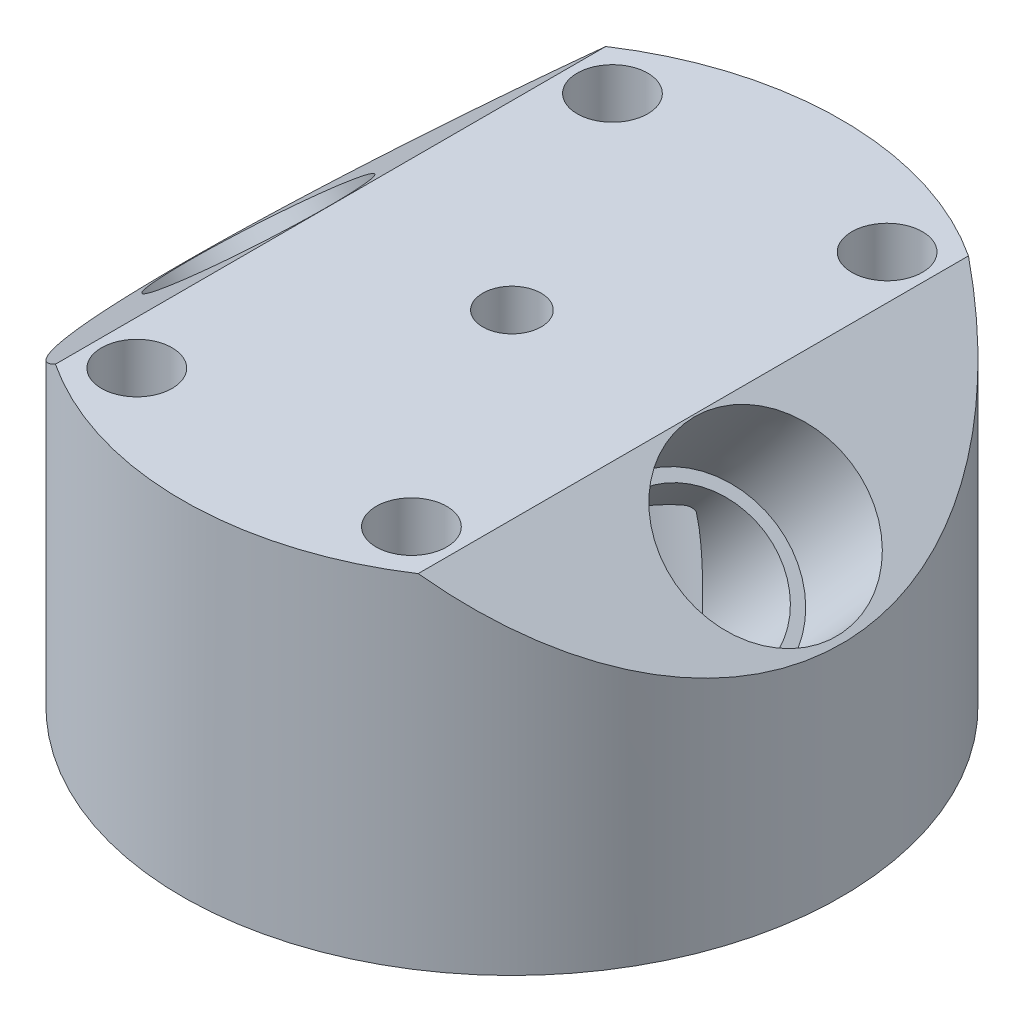
SolidWorks part; units mm, degrees
material "AISI 304"
ref_plane "Front Plane" through (0, 0, 0) normal (0, 0, 1) x (1, 0, 0)
ref_plane "Top Plane" through (0, 0, 0) normal (0, 1, 0) x (1, 0, 0)
ref_plane "Right Plane" through (0, 0, 0) normal (1, 0, 0) x (0, 0, -1)
sketch "MASTER" plane through (0, 0, 0) normal (0, 0, 1) x (1, 0, 0)
  line L0 (0, 0) -> (0, 38.1) construction
  line L1 (0, 38.1) -> (-30.48, 38.1)
  line L2 (-30.48, 38.1) -> (-30.48, 0)
  line L3 (-30.48, 0) -> (-12.7, 0)
  line L4 (-12.7, 0) -> (-12.7, 19.05)
  line L5 (-6.3246, 19.05) -> (-4.7625, 17.4879)
  line L6 (-4.7625, 17.4879) -> (0, 17.4879)
  line L7 (-6.3246, 19.05) -> (-12.7, 19.05)
  line L8 (-12.7, 0) -> (0, 0) construction
  line L9 (0, 38.1) -> (0, 17.4879)
  line L10 (33.1516, -30.216) -> (-31.067, 46.3167) construction
  line L11 (21.713, -38.7917) -> (-42.0021, 37.1411) construction
  line L12 (-7.4178, 18.1327) -> (-6.3246, 19.05) construction
  line L13 (-11.6068, 0.9173) -> (-12.7, 0) construction
  line L14 (-36.5346, 41.7289) -> (-21.8455, 24.2232) construction
  line L15 (-31.067, 46.3167) -> (-42.0021, 37.1411) construction
  point P18 (33.1336, -30.2098)
  point P19 (21.6951, -38.7855)
  dimension "D1" = 6.3754
  dimension "D2" = 38.1
  dimension "D3" = 60.96
  dimension "D4" = 25.4
  dimension "D5" = 19.05
  dimension "D6" = 9.525
  dimension "D7" = 135
  dimension "D8" = 14.2748
  dimension "D9" = 50
revolve "MASTER_SKETCH" add sketch "MASTER" angle 360 about L9
sketch "Sketch2" plane through (0, 0, 0) normal (0, 0, 1) x (1, 0, 0)
  line L0 (-30.48, 20.2483) -> (-9.2051, 38.1)
  line L1 (-30.48, 38.1) -> (-30.48, 0) construction
  line L3 (0, 38.1) -> (-30.48, 38.1) construction
  line L4 (21.713, -38.7917) -> (-42.0021, 37.1411) construction
  line L5 (-30.48, 20.2483) -> (-30.48, 38.1)
  line L6 (-30.48, 38.1) -> (-9.2051, 38.1)
  line L7 (0, 0) -> (0, 44.6314) construction
  line L8 (30.48, 38.1) -> (9.2051, 38.1)
  line L9 (30.48, 20.2483) -> (30.48, 38.1)
  line L10 (30.48, 20.2483) -> (9.2051, 38.1)
  dimension "D1" = 2.032
extrude "Cut-Extrude1" cut sketch "Sketch2" against normal through all both and the other way through all
hole_wizard "1/4-28 Tapped Hole1" positions "Sketch3" profile "Sketch4" tap size "1/4-28" standard "ANSI Inch" end condition through all
sketch "Sketch3" plane through (0, 38.1, 0) normal (0, 1, 0) x (1, 0, 0)
  point P0 (0, 0)
sketch "Sketch4" plane through (0, 38.1, 0) normal (1, 0, 0) x (0, 0, 1)
  line L0 (0, 0) -> (0, 38.1)
  line L1 (0, 38.1) -> (2.7051, 38.1)
  line L2 (2.7051, 38.1) -> (2.7051, 0)
  line L5 (2.7051, 0) -> (0, 0)
  line L11 (0, -6.35) -> (0, 107.95) construction
  dimension "Thru Tap Drill Dia." = 5.4102
  dimension "Thru Tap Drill Depth" = 38.1
cosmetic thread "Hole Thread1" parameters "D2"=6.35
sketch "Sketch5" plane through (0, 38.1, 0) normal (0, 1, 0) x (1, 0, 0)
  circle A0 centre (0, 0) radius 30.48
  dimension "D1" = 60.96
extrude "Cut-Extrude2" cut sketch "Sketch5" against normal blind 6.35
fillet "use-round-corner-endmill" radius 0.762 2 edges at (-6.3246, 19.05, 0) (-12.7, 19.05, 0)
hole_wizard "3/8 NPT Tapped Hole1" positions "Sketch6" profile "Sketch7" size "3/8" standard "ANSI Inch" end condition through all
sketch "Sketch6" plane through (-22.5639, 26.8906, 0) normal (-0.6428, 0.766, 0) x (0.766, 0.6428, 0)
  point P0 (-1.1643, 0)
sketch "Sketch7" plane through (-23.4558, 26.1423, 0) normal (0, 0, 1) x (-0.766, -0.6428, 0)
  line L0 (0, 0) -> (0, 54.6954)
  line L1 (0, 54.6954) -> (7.1374, 54.6954)
  line L2 (-8.2632, 10.414) -> (-8.575, 0) construction
  line L3 (7.1374, 54.6954) -> (7.1374, 10.414)
  line L4 (7.1374, 10.414) -> (8.2632, 10.414)
  line L5 (8.2632, 10.414) -> (8.575, 0)
  line L7 (8.575, 0) -> (0, 0)
  line L8 (0, -6.35) -> (0, 107.95) construction
  line L11 (-7.1374, 10.414) -> (-8.2632, 10.414) construction
  dimension "Thru Tap Drill Dia." = 14.2748
  dimension "Thru Tap Drill Depth" = 54.6954
  dimension "Thread Dia." = 17.15
  dimension "Thread Angle" = 3.43
  dimension "Thread Depth" = 10.414
mirror "Mirror1" about plane through (0, 0, 0) normal (1, 0, 0) of "3/8 NPT Tapped Hole1"
hole_wizard "1/4 Clearance Hole1" positions "Sketch9" profile "Sketch10" hole size "1/4" standard "ANSI Inch" end condition through all
sketch "Sketch9" plane through (0, 31.75, 0) normal (0, 1, 0) x (1, 0, 0)
  line L1 (12.7, -21.997) -> (25.4, 0)
  line L2 (25.4, 0) -> (12.7, 21.997)
  line L3 (12.7, 21.997) -> (-12.7, 21.997)
  line L4 (-12.7, 21.997) -> (-25.4, 0)
  line L5 (-25.4, 0) -> (-12.7, -21.997)
  line L6 (-12.7, -21.997) -> (12.7, -21.997)
  circle A0 centre (0, 0) radius 25.4 construction
  point P3 (12.7, -21.997)
  point P5 (12.7, 21.997)
  point P6 (-12.7, 21.997)
  point P8 (-12.7, -21.997)
  dimension "D1" = 50.8
sketch "Sketch10" plane through (-12.7, 31.75, 21.997) normal (1, 0, 0) x (0, 0, 1)
  line L0 (0, 0) -> (0, 31.75)
  line L1 (0, 31.75) -> (3.2639, 31.75)
  line L2 (3.2639, 31.75) -> (3.2639, 0)
  line L5 (3.2639, 0) -> (0, 0)
  line L11 (0, -6.35) -> (0, 107.95) construction
  dimension "Thru Hole Dia." = 6.5278
  dimension "Thru Hole Depth" = 31.75
